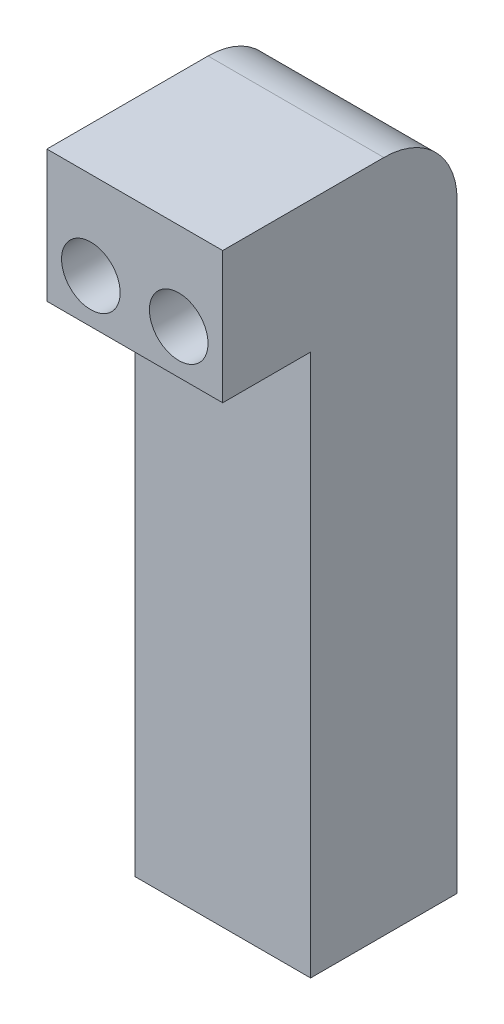
SolidWorks part; units mm, degrees
ref_plane "Спереди" through (0, 0, 0) normal (0, 0, 1) x (1, 0, 0)
ref_plane "Сверху" through (0, 0, 0) normal (0, 1, 0) x (1, 0, 0)
ref_plane "Справа" through (0, 0, 0) normal (1, 0, 0) x (0, 0, -1)
other "Configuration Table"
sketch "Эскиз1" plane through (0, 0, 0) normal (0, 1, 0) x (1, 0, 0)
  line L0 (-6, 0) -> (-6, -10) construction
  line L1 (0, 0) -> (-1, 0)
  line L2 (0, 0) -> (0, -10)
  line L3 (0, -10) -> (-12, -10)
  line L4 (-12, 0) -> (-12, -10)
  line L5 (-11, -4) -> (-11, 0)
  line L6 (-7, -4) -> (-7, 0)
  line L7 (-5, -4) -> (-5, 0)
  line L8 (-1, -4) -> (-1, 0)
  line L9 (-11, 0) -> (-12, 0)
  line L10 (-5, 0) -> (-7, 0)
  arc A0 (-11, -4) -> (-7, -4) centre (-9, -4) ccw
  arc A1 (-1, -4) -> (-5, -4) centre (-3, -4) cw
  dimension "D3" = 4
  dimension "D1" = 12
  dimension "D2" = 10
  dimension "D4" = 1
  dimension "D5" = 4
extrude "Бобышка-Вытянуть1" add sketch "Эскиз1" along normal blind 40
sketch "Эскиз2" plane through (0, 40, 0) normal (0, 1, 0) x (1, 0, 0)
  line L1 (-12, 0) -> (0, 0)
  line L2 (-12, 0) -> (-12, -10)
  line L3 (-12, -10) -> (0, -10)
  line L4 (0, 0) -> (0, -10)
extrude "Бобышка-Вытянуть2" add sketch "Эскиз2" along normal blind 6
sketch "Эскиз4" plane through (0, 0, 10) normal (0, 0, 1) x (1, 0, 0)
  line L0 (0, 46) -> (0, 0) construction
  line L1 (-12, 46) -> (0, 46)
  line L2 (-12, 46) -> (-12, 37)
  line L3 (-12, 37) -> (0, 37)
  line L4 (0, 46) -> (0, 37)
  dimension "D1" = 9
extrude "Бобышка-Вытянуть3" add sketch "Эскиз4" along normal blind 6
fillet "Скругление1" radius 5 1 edges at (-6, 46, 0)
sketch "Эскиз3" plane through (0, 0, 0) normal (0, 0, -1) x (-1, 0, 0)
  line L0 (6, 41) -> (6, 46) construction
  line L1 (12, 41) -> (0, 41) construction
  line L2 (0, 46) -> (12, 46) construction
  line L3 (1, 40) -> (5, 40) construction
  line L4 (5, 40) -> (5, 0) construction
  circle A0 centre (3, 40) radius 2
  circle A1 centre (9, 40) radius 2
  point P8 (0, 0)
extrude "Вырез-Вытянуть2" cut sketch "Эскиз3" against normal through all
fillet "Скругление3" radius 2 2 edges at (-9, 38, 6) (-3, 38, 6)
